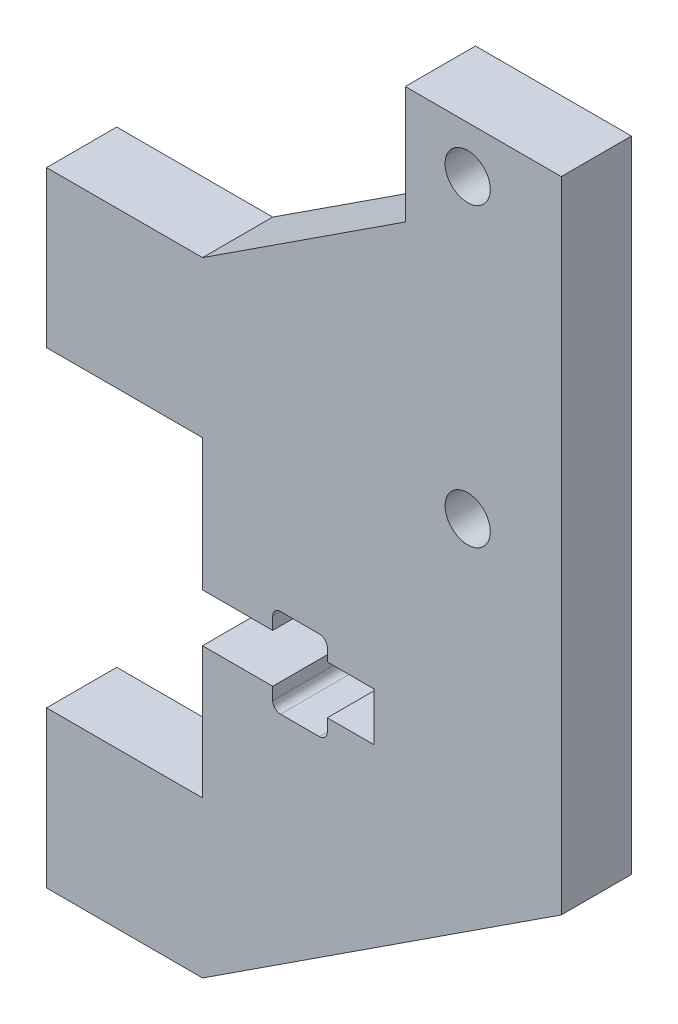
SolidWorks part; units mm, degrees
ref_plane "Front Plane" through (0, 0, 0) normal (0, 0, 1) x (1, 0, 0)
ref_plane "Top Plane" through (0, 0, 0) normal (0, 1, 0) x (1, 0, 0)
ref_plane "Right Plane" through (0, 0, 0) normal (1, 0, 0) x (0, 0, -1)
sketch "Sketch1" plane through (0, 0, 0) normal (0, 0, 1) x (1, 0, 0)
  line L0 (13, 3.4783) -> (0, -5)
  line L1 (0, -5) -> (-10, -5)
  line L2 (-10, -5) -> (-10, -15)
  line L3 (-10, -15) -> (0, -15)
  line L4 (0, -15) -> (0, -35)
  line L5 (0, -35) -> (-10, -35)
  line L6 (-10, -35) -> (-10, -45)
  line L7 (-10, -45) -> (0, -45)
  line L10 (0, -45) -> (23, -30)
  line L11 (23, -30) -> (23, 11)
  line L12 (23, 11) -> (13, 11)
  line L13 (13, 11) -> (13, 3.4783)
  line L15 (0, -5) -> (0, -45) construction
  line L16 (-10, -10) -> (0, -10) construction
  line L17 (-10, -40) -> (0, -40) construction
  line L18 (-10, -15) -> (-10, -35) construction
  line L19 (-10, -25) -> (0, -25) construction
  dimension "D1" = 10
  dimension "D2" = 10
  dimension "D3" = 10
  dimension "D4" = 10
  dimension "D5" = 15
  dimension "D8" = 10
  dimension "D10" = 13
  dimension "D6" = 15
  dimension "D7" = 16
extrude "Boss-Extrude1" add sketch "Sketch1" along normal blind 4.5
sketch "Sketch2" plane through (0, 0, 4.5) normal (0, 0, 1) x (1, 0, 0)
  line L0 (0, -25) -> (23, -25) construction
  line L1 (0, -15) -> (0, -35) construction
  line L3 (11, -26.55) -> (11, -23.45) construction
  line L4 (11, -23.45) -> (0, -23.45) construction
  line L5 (0, -26.55) -> (0, -23.45)
  line L6 (0, -23.45) -> (4.5, -23.45)
  line L7 (4.5, -23.45) -> (4.5, -22.65)
  line L8 (5, -22.15) -> (7.5, -22.15)
  line L9 (8, -22.65) -> (8, -23.45)
  line L10 (8, -23.45) -> (11, -23.45)
  line L11 (11, -23.45) -> (11, -26.55)
  line L12 (11, -26.55) -> (0, -26.55) construction
  line L13 (8, -26.55) -> (11, -26.55)
  line L14 (8, -27.35) -> (8, -26.55)
  line L15 (5, -27.85) -> (7.5, -27.85)
  line L16 (4.5, -26.55) -> (4.5, -27.35)
  line L17 (0, -26.55) -> (4.5, -26.55)
  line L18 (23, -30) -> (23, 11) construction
  arc A0 (7.5, -22.15) -> (8, -22.65) centre (7.5, -22.65) cw
  arc A1 (4.5, -22.65) -> (5, -22.15) centre (5, -22.65) cw
  arc A2 (4.5, -27.35) -> (5, -27.85) centre (5, -27.35) ccw
  arc A3 (7.5, -27.85) -> (8, -27.35) centre (7.5, -27.35) ccw
  point P15 (8, -22.15)
  point P18 (4.5, -22.15)
  point P27 (11, -25)
  point P29 (4.5, -27.85)
  point P30 (8, -27.85)
  dimension "D6" = 0.5
  dimension "D1" = 11
  dimension "D2" = 1.55
  dimension "D3" = 8
  dimension "D4" = 3.5
  dimension "D5" = 2.85
extrude "screw-cutout" cut sketch "Sketch2" against normal through all
sketch "Sketch3" plane through (0, 0, 4.5) normal (0, 0, 1) x (1, 0, 0)
  line L0 (17, 55) -> (17, -45) construction
  line L3 (13, 11) -> (13, 3.4783) construction
  line L5 (-10, -45) -> (0, -45) construction
  line L10 (11, -26.55) -> (11, -23.45) construction
  circle A1 centre (17, 8) radius 1.45
  circle A5 centre (17, -11) radius 1.45
  point P8 (11, -25)
  dimension "D4" = 2.9
  dimension "D11" = 2.9
  dimension "D6" = 4
  dimension "D12" = 19
  dimension "D2" = 14
extrude "Cut-Extrude2" cut sketch "Sketch3" against normal through all
sketch "Sketch4" [suppressed] plane through (0, 0, 4.5) normal (0, 0, 1) x (1, 0, 0)
  line L0 (17, -11) -> (17, 8) construction
  line L1 (17, -1.5) -> (13, -1.5) construction
  line L2 (13, 11) -> (13, 3.4783) construction
  line L4 (15, 2.5) -> (13, 2.5)
  line L5 (15, 2.5) -> (15, -5.5)
  line L6 (15, -5.5) -> (13, -5.5)
  line L7 (13, 2.5) -> (13, -5.5)
  line L8 (15, 2.5) -> (13, -5.5) construction
  line L9 (15, -5.5) -> (13, 2.5) construction
  circle A1 centre (17, 8) radius 1.55 construction
  circle A3 centre (17, -11) radius 1.55 construction
  point P11 (14, -1.5)
  dimension "D1" = 8
  dimension "D2" = 2
  dimension "D3" = 3
equation "\"X-ROD-SPACING\"=45"
equation "\"Y-ROD-SPACING\"=75"
equation "\"Z-ROD-SPACING\"=17.5"
equation "\"Y-BED-OFFSET\"=2"
equation "\"Y-BED-ROD-INSET\"=3.5"
equation "\"T-SLOT-NUT-FILLET-RADIUS\"=0.5"
equation "\"T-SLOT-SCREW-SHAFT-RADIUS\"=1.55"
equation "\"T-SLOT-SCREW-SHAFT-CUTOUT-LENGTH\"=11"
equation "\"T-SLOT-NUT-DEPTH\"=3.5"
equation "\"T-SLOT-NUT-WIDTH\"=2.85"
equation "\"T-SLOT-NUT-END-DISTANCE\"=8"
equation "\"ACRYLIC-THICKNESS\"=10"
equation "\"ACRYLIC-THICKNESS2\"=4.5"
equation "\"ACRYLIC-TAB-CUTOUT-SIZE\"=\"ACRYLIC-THICKNESS\"+\"ACRYLIC-TAB-TOLERANCE\"*2"
equation "\"ACRYLIC-TAB-WIDTH\"=\"ACRYLIC-THICKNESS\""
equation "\"ACRYLIC-M3-HOLE\"=2.9"
equation "\"SMOOTHROD-CAP-SCREW-DISTANCE\"=20"
equation "\"FRAME-WIDTH-INNER\"=370"
equation "\"NEMA17-HOLE-SPACING\"=31"
equation "\"NEMA17-CENTRAL-CUTOUT\"=22.5"
equation "\"Z-BRACKET-REACH\"=57"
equation "\"Z-ROD-INSET\"=13.5"
equation "\"TOP-BRACKET-SPACING\"=40"
equation "\"SMOOTHROD-X-LENGTH\"=350"
equation "\"SMOOTHROD-Y-LENGTH\"=350"
equation "\"SMOOTHROD-Z-LENGTH\"=350"
equation "\"SMOOTHROD-TIGHTENING-HEADROOM\"=.25"
equation "\"LEADSCREW-Z-LENGTH\"=300"
equation "\"SCREW-LENGTH-FRAME\"=\"ACRYLIC-THICKNESS\" + 10"
equation "\"SCREW-HEAD-RADIUS\"=6"
equation "\"PRINTED-X-SMOOTHROD-DIAMETER\"=8.8"
equation "\"PRINTED-X-SMOOTHROD-CUTOUT\"=10"
equation "\"PRINTED-X-BASE-HEIGHT\"=10"
equation "\"PRINTED-LM8UU-CUTOUT-SIZE\"=15.5"
equation "\"PRINTED-LM8UU-CUTOUT-LENGTH\"=24.5"
equation "\"PRINTED-X-IDLER-HEIGHT\"=16"
equation "\"PSU-MOUNTING-WIDTH\"=95"
equation "\"PSU-MOUNTING-HEIGHT\"=177"
equation "\"Y-BELT-TO-ROD-DISTANCE\"=20"
equation "\"SPOOL-HOLDER-ROD-SPACING\"=150"
equation "\"D1@Sketch1\"=\"ACRYLIC-TAB-WIDTH\""
equation "\"D2@Sketch1\"=\"ACRYLIC-TAB-WIDTH\""
equation "\"D3@Sketch1\"=\"ACRYLIC-THICKNESS\""
equation "\"D4@Sketch1\"=\"ACRYLIC-THICKNESS\""
equation "\"D1@Boss-Extrude1\"=\"ACRYLIC-THICKNESS2\""
equation "\"D1@Sketch2\"=\"T-SLOT-SCREW-SHAFT-CUTOUT-LENGTH\""
equation "\"D2@Sketch2\"=\"T-SLOT-SCREW-SHAFT-RADIUS\""
equation "\"D3@Sketch2\"=\"T-SLOT-NUT-END-DISTANCE\""
equation "\"D4@Sketch2\"=\"T-SLOT-NUT-DEPTH\""
equation "\"D5@Sketch2\"=\"T-SLOT-NUT-WIDTH\""
equation "\"D6@Sketch2\"=\"T-SLOT-NUT-FILLET-RADIUS\""
equation "\"D4@Sketch3\"=\"ACRYLIC-M3-HOLE\""
equation "\"D11@Sketch3\"=\"ACRYLIC-M3-HOLE\""
equation "\"Y-BED-SCREW-SPACING\"=209"
equation "\"Y-BED-SCREW-CUTOUT-SLOT-HEIGHT\"=2"
equation "\"ACRYLIC-TAB-TOLERANCE\"=-.05"
equation "\"SCREW-LENGTH-MOTOR\"=\"ACRYLIC-THICKNESS\" + 5"
equation "\"SCREW-LENGTH-EXTRUDER\"=28"
equation "\"PRINTED-M3-HOLE\"=3.5"
equation "\"ACRYLIC-X-CARRIAGE-WIDTH\"=55"
equation "\"ACRYLIC-X-CARRIAGE-HEIGHT\"=75"
equation "\"ACRYLIC-X-CARRIAGE-LM8UU-CUTOUT-WIDTH\"=24.25"
equation "\"ACRYLIC-X-CARRIAGE-LM8UU-CUTOUT-HEIGHT\"=11.0"
equation "\"ACRYLIC-X-CARRIAGE-SCREW-SPACING-X\"=15"
equation "\"ACRYLIC-X-CARRIAGE-SCREW-SPACING-Y\"=33"
equation "\"ACRYLIC-X-CARRIAGE-CENTER-TAB-SPACING\"=14"
equation "\"ACRYLIC-X-CARRIAGE-EXTRUDER-OFFSET\"=26"
equation "\"ACRYLIC-X-CARRIAGE-EXTRUDER-ANGLE\"=90"
equation "\"ACRYLIC-X-CARRIAGE-EXTRUDER-SHELF-DEPTH\"=\"ACRYLIC-X-CARRIAGE-EXTRUDER-OFFSET\" + 28"
equation "\"ACRYLIC-X-CARRIAGE-EXTRUDER-BRACE-SPACING\"=23"
equation "\"ACRYLIC-X-CARRIAGE-EXTRUDER-BRACE-TAB-OFFSET\"=20"
equation "\"ACRYLIC-X-CARRIAGE-EXTRUDER-BRACE-HEIGHT\"=35"
equation "\"ACRYLIC-X-CARRIAGE-EXTRUDER-BRACE-SCREW-SPACING\"=22"
equation "\"ACRYLIC-X-CARRIAGE-DUAL-WIDTH-MULTIPLIER\"=1.65"
equation "\"ACRYLIC-X-CARRIAGE-DUAL-HOTEND-SPACING\"=42"
equation "\"ACRYLIC-X-CARRIAGE-DUAL-WIDTH\"=75"
equation "\"ACRYLIC-X-CARRIAGE-DUAL-HOTEND-SEPARATION\"=36"
equation "\"ACRYLIC-X-CARRIAGE-DUAL-MOUNT-PLATE-DEPTH\"=75"
equation "\"ACRYLIC-X-CARRIAGE-DUAL-MOUNT-BRACE-WIDTH\"=33"
equation "\"ACRYLIC-X-CARRIAGE-DUAL-MOUNT-SCREW-WIDTH\"=40"
equation "\"BLOWER-FAN-WIDTH\"=15"
